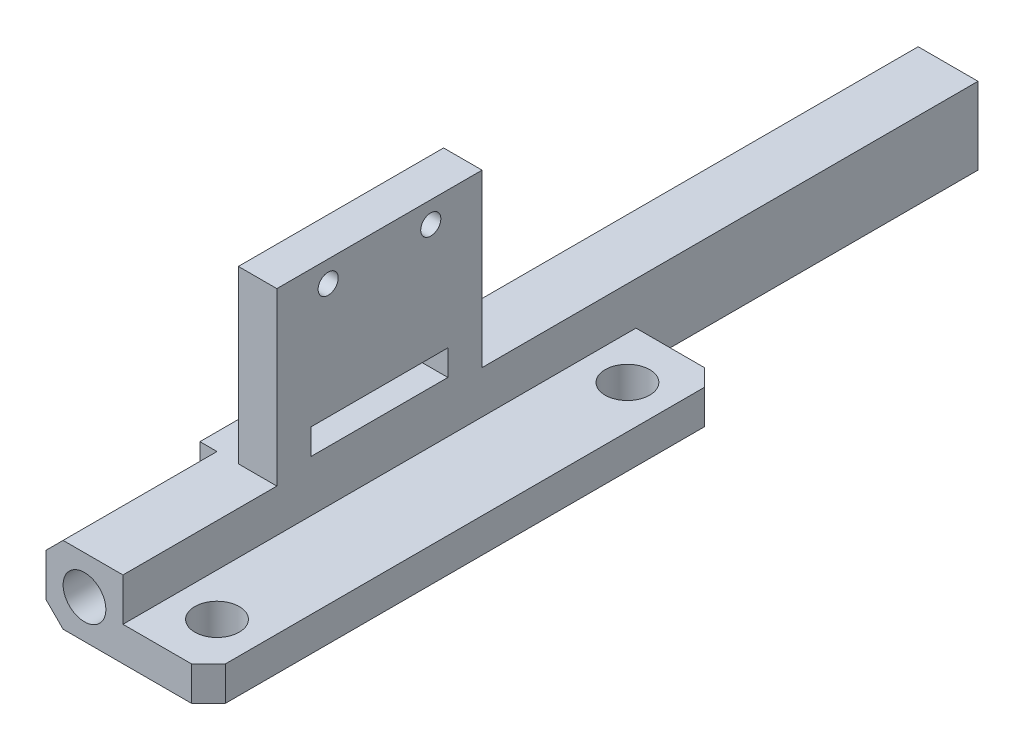
SolidWorks part; units mm, degrees
ref_plane "Front Plane" through (0, 0, 0) normal (0, 0, 1) x (1, 0, 0)
ref_plane "Top Plane" through (0, 0, 0) normal (0, 1, 0) x (1, 0, 0)
ref_plane "Right Plane" through (0, 0, 0) normal (1, 0, 0) x (0, 0, -1)
sketch "Sketch1" plane through (0, 0, 0) normal (0, 1, 0) x (1, 0, 0)
  line L1 (0, 0) -> (77.47, 0)
  line L2 (0, 0) -> (0, 127)
  line L3 (0, 127) -> (77.47, 127)
  line L4 (77.47, 0) -> (77.47, 127)
  dimension "D1" = 77.47
  dimension "D2" = 127
extrude "Boss-Extrude1" add sketch "Sketch1" along normal blind 11.43
sketch "Sketch2" plane through (0, 0, 0) normal (0, 0, 1) x (1, 0, 0)
  line L0 (5.715, 5.715) -> (71.755, 5.715) construction
  line L1 (38.735, 11.43) -> (38.735, 0) construction
  line L2 (0, 11.43) -> (77.47, 11.43) construction
  line L3 (0, 0) -> (77.47, 0) construction
  circle A0 centre (5.715, 5.715) radius 3.175
  circle A1 centre (71.755, 5.715) radius 3.175
  point P10 (38.735, 5.715)
  dimension "D1" = 6.35
  dimension "D2" = 66.04
extrude "Cut-Extrude1" cut sketch "Sketch2" against normal through all
sketch "Sketch3" plane through (0, 11.43, 0) normal (0, 1, 0) x (1, 0, 0)
  line L0 (11.43, 127) -> (11.43, 88.9)
  line L1 (77.47, 127) -> (0, 127) construction
  line L2 (11.43, 127) -> (66.04, 127)
  line L3 (66.04, 127) -> (66.04, 88.9)
  line L4 (53.34, 76.2) -> (24.13, 76.2)
  line L5 (0, 127) -> (0, 0) construction
  arc A0 (66.04, 88.9) -> (53.34, 76.2) centre (53.34, 88.9) cw
  arc A1 (24.13, 76.2) -> (11.43, 88.9) centre (24.13, 88.9) cw
  point P10 (38.735, 127)
  dimension "D1" = 12.7
  dimension "D2" = 11.43
  dimension "D3" = 50.8
extrude "Cut-Extrude2" cut sketch "Sketch3" against normal through all
sketch "Sketch4" plane through (0, 0, -127) normal (0, 0, -1) x (-1, 0, 0)
  line L0 (-11.43, 0) -> (-11.43, 11.43) construction
  line L1 (-66.04, 11.43) -> (-11.43, 11.43)
  line L2 (-66.04, 11.43) -> (-66.04, 5.08)
  line L3 (-66.04, 5.08) -> (-11.43, 5.08)
  line L4 (-11.43, 11.43) -> (-11.43, 5.08)
  line L5 (-11.43, 0) -> (0, 0) construction
  dimension "D1" = 5.08
extrude "Cut-Extrude3" cut sketch "Sketch4" against normal through all
chamfer "Chamfer1" distance 2.54 angle 45 4 edges at (0, 0, -63.5) (0, 11.43, -63.5) (77.47, 0, -63.5) (77.47, 11.43, -63.5)
sketch "Sketch5" plane through (0, 11.43, 0) normal (0, 1, 0) x (1, 0, 0)
  line L0 (11.43, 88.9) -> (11.43, 76.2)
  line L1 (11.43, 0) -> (11.43, 88.9) construction
  line L2 (11.43, 76.2) -> (77.47, 76.2)
  line L3 (77.47, 127) -> (77.47, 0) construction
  line L4 (77.47, 76.2) -> (77.47, 127)
  line L8 (24.13, 76.2) -> (53.34, 76.2) construction
  line L9 (77.47, 127) -> (11.43, 127)
  line L10 (11.43, 127) -> (11.43, 88.9)
extrude "Cut-Extrude4" cut sketch "Sketch5" against normal through all
sketch "Sketch6" plane through (0, 11.43, 0) normal (0, 1, 0) x (1, 0, 0)
  line L0 (24.13, 76.2) -> (24.13, 0)
  line L1 (11.43, 76.2) -> (66.04, 76.2) construction
  line L2 (66.04, 0) -> (11.43, 0) construction
  line L3 (24.13, 0) -> (77.47, 0)
  line L4 (77.47, 0) -> (77.47, 76.2)
  line L5 (77.47, 76.2) -> (24.13, 76.2)
  line L6 (11.43, 0) -> (11.43, 76.2) construction
  dimension "D1" = 12.7
extrude "Cut-Extrude5" cut sketch "Sketch6" against normal through all
sketch "Sketch7" plane through (0, 5.08, 0) normal (0, 1, 0) x (1, 0, 0)
  line L0 (11.43, 76.2) -> (24.13, 76.2) construction
  circle A0 centre (17.78, 68.58) radius 3.302
  circle A1 centre (17.78, 7.62) radius 3.302
  point P5 (17.78, 76.2)
  point P6 (0, 0)
  point P11 (0, 0)
  dimension "D1" = 6.604
  dimension "D2" = 7.62
  dimension "D3" = 68.58
extrude "Cut-Extrude6" cut sketch "Sketch7" against normal through all
chamfer "Chamfer2" distance 2.54 angle 45 2 edges at (24.13, 2.54, -76.2) (24.13, 2.54, 0)
ref_plane "Plane1" through (0, 0, -38.1) normal (0, 0, 1) x (1, 0, 0)
sketch "Sketch12" plane through (0, 0, -38.1) normal (0, 0, 1) x (1, 0, 0)
  line L0 (0, 0) -> (0, 8.89) construction
  line L1 (0, 8.89) -> (0, 36.83)
  line L2 (0, 36.83) -> (11.43, 36.83)
  line L3 (11.43, 36.83) -> (11.43, 11.43)
  line L5 (11.43, 11.43) -> (2.54, 11.43)
  line L6 (2.54, 11.43) -> (0, 8.89)
  point P7 (0, 0)
  point P9 (0, 0)
  point P12 (0, 0)
  dimension "D1" = 25.4
extrude "Boss-Extrude3" add sketch "Sketch12" along normal blind 15.24
mirror "Mirror1" about plane through (0, 0, -38.1) normal (0, 0, 1) of "Boss-Extrude3"
sketch "Sketch13" plane through (0, 0, -22.86) normal (0, 0, 1) x (1, 0, 0)
  line L0 (0, 36.83) -> (5.715, 36.83)
  line L1 (11.43, 36.83) -> (0, 36.83) construction
  line L2 (5.715, 36.83) -> (5.715, 11.43)
  line L3 (2.54, 11.43) -> (11.43, 11.43) construction
  line L4 (5.715, 11.43) -> (0, 11.43)
  line L5 (0, 36.83) -> (0, 8.89) construction
  line L6 (0, 11.43) -> (0, 36.83)
extrude "Cut-Extrude9" cut sketch "Sketch13" against normal up to next
sketch "Sketch14" plane through (5.715, 0, 0) normal (-1, 0, 0) x (0, 0, 1)
  line L1 (-45.72, 33.655) -> (-30.48, 33.655) construction
  line L3 (-53.34, 36.83) -> (-22.86, 36.83) construction
  line L5 (-48.26, 16.51) -> (-27.94, 16.51)
  line L6 (-27.94, 16.51) -> (-27.94, 12.7)
  line L7 (-27.94, 12.7) -> (-48.26, 12.7)
  line L8 (-48.26, 12.7) -> (-48.26, 16.51)
  circle A0 centre (-45.72, 33.655) radius 1.4928
  circle A1 centre (-30.48, 33.655) radius 1.4928
  point P4 (-38.1, 33.655)
  point P5 (0, 0)
  point P6 (0, 0)
  point P14 (-38.1, 36.83)
  point P15 (-38.1, 16.51)
  dimension "D1" = 2.9857
  dimension "D3" = 15.24
  dimension "D4" = 3.175
  dimension "D5" = 20.32
  dimension "D7" = 24.13
  dimension "D2" = 2.54
  dimension "D6" = 20.32
extrude "Cut-Extrude10" cut sketch "Sketch14" against normal up to next
equation "\"D2@Sketch14\"=0.5*(\"D5@Sketch14\"-\"D3@Sketch14\")"
